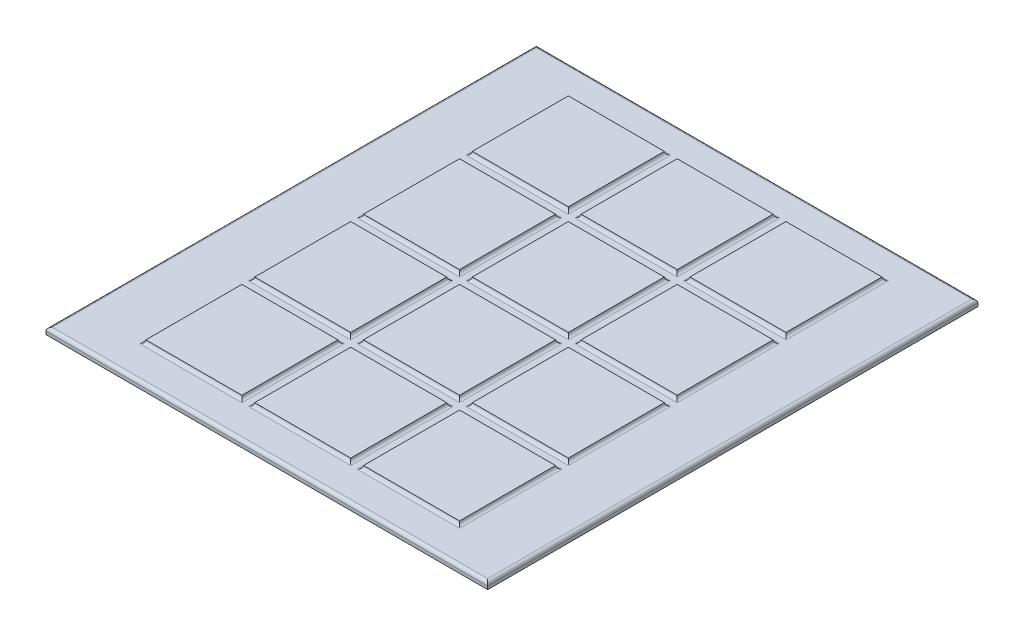
SolidWorks part; units mm, degrees
ref_plane "Front Plane" through (0, 0, 0) normal (0, 0, 1) x (1, 0, 0)
ref_plane "Top Plane" through (0, 0, 0) normal (0, 1, 0) x (1, 0, 0)
ref_plane "Right Plane" through (0, 0, 0) normal (1, 0, 0) x (0, 0, -1)
sketch "Sketch1" plane through (0, 0, 0) normal (0, 1, 0) x (1, 0, 0)
  line L1 (-34.5, 38.3) -> (34.5, 38.3)
  line L2 (-34.5, 38.3) -> (-34.5, -38.3)
  line L3 (-34.5, -38.3) -> (34.5, -38.3)
  line L4 (34.5, 38.3) -> (34.5, -38.3)
  point P4 (-34.5, 0)
  point P6 (0, 38.3)
  dimension "D1" = 76.6
  dimension "D2" = 69
extrude "Boss-Extrude1" add sketch "Sketch1" along normal blind 1 contours L2 L3 L4 L1
sketch "Sketch2" plane through (0, 1, 0) normal (0, 1, 0) x (1, 0, 0)
  line L0 (-24.5, 16.3) -> (-9.5, 16.3)
  line L1 (-24.5, 33.3) -> (-9.5, 33.3)
  line L2 (-24.5, 33.3) -> (-24.5, 18.3)
  line L3 (-24.5, 18.3) -> (-9.5, 18.3)
  line L4 (-9.5, 33.3) -> (-9.5, 18.3)
  line L5 (-7.5, 33.3) -> (7.5, 33.3)
  line L6 (-7.5, 33.3) -> (-7.5, 18.3)
  line L7 (-7.5, 18.3) -> (7.5, 18.3)
  line L8 (7.5, 33.3) -> (7.5, 18.3)
  line L9 (9.5, 33.3) -> (24.5, 33.3)
  line L10 (9.5, 33.3) -> (9.5, 18.3)
  line L11 (9.5, 18.3) -> (24.5, 18.3)
  line L12 (24.5, 33.3) -> (24.5, 18.3)
  line L13 (-24.5, 16.3) -> (-24.5, 1.3)
  line L14 (-24.5, 1.3) -> (-9.5, 1.3)
  line L15 (-9.5, 16.3) -> (-9.5, 1.3)
  line L16 (-7.5, 16.3) -> (7.5, 16.3)
  line L17 (-7.5, 16.3) -> (-7.5, 1.3)
  line L18 (-7.5, 1.3) -> (7.5, 1.3)
  line L19 (7.5, 16.3) -> (7.5, 1.3)
  line L20 (9.5, 16.3) -> (24.5, 16.3)
  line L21 (9.5, 16.3) -> (9.5, 1.3)
  line L22 (9.5, 1.3) -> (24.5, 1.3)
  line L23 (24.5, 16.3) -> (24.5, 1.3)
  line L24 (-24.5, -0.7) -> (-9.5, -0.7)
  line L25 (-24.5, -0.7) -> (-24.5, -15.7)
  line L26 (-24.5, -15.7) -> (-9.5, -15.7)
  line L27 (-9.5, -0.7) -> (-9.5, -15.7)
  line L28 (-7.5, -0.7) -> (7.5, -0.7)
  line L29 (-7.5, -0.7) -> (-7.5, -15.7)
  line L30 (-7.5, -15.7) -> (7.5, -15.7)
  line L31 (7.5, -0.7) -> (7.5, -15.7)
  line L32 (9.5, -0.7) -> (24.5, -0.7)
  line L33 (9.5, -0.7) -> (9.5, -15.7)
  line L34 (9.5, -15.7) -> (24.5, -15.7)
  line L35 (24.5, -0.7) -> (24.5, -15.7)
  line L36 (-24.5, -17.7) -> (-9.5, -17.7)
  line L37 (-24.5, -17.7) -> (-24.5, -32.7)
  line L38 (-24.5, -32.7) -> (-9.5, -32.7)
  line L39 (-9.5, -17.7) -> (-9.5, -32.7)
  line L40 (-7.5, -17.7) -> (7.5, -17.7)
  line L41 (-7.5, -17.7) -> (-7.5, -32.7)
  line L42 (-7.5, -32.7) -> (7.5, -32.7)
  line L43 (7.5, -17.7) -> (7.5, -32.7)
  line L44 (9.5, -17.7) -> (24.5, -17.7)
  line L45 (9.5, -17.7) -> (9.5, -32.7)
  line L46 (9.5, -32.7) -> (24.5, -32.7)
  line L47 (24.5, -17.7) -> (24.5, -32.7)
  line L48 (-34.5, 38.3) -> (34.5, 38.3) construction
  point P13 (0, 33.3)
  dimension "D1" = 2
  dimension "D2" = 2
  dimension "D3" = 15
  dimension "D4" = 4
  dimension "D5" = 5
extrude "Boss-Extrude2" add sketch "Sketch2" along normal blind 0.5
fillet "Fillet1" radius 0.5 52 edges at (17, 1, 32.7) (24.5, 1, 25.2) (17, 1, 17.7) (9.5, 1, 25.2) (-17, 1, 32.7) (-9.5, 1, 25.2) (-17, 1, 17.7) (-24.5, 1, 25.2) (0, 1, 15.7) (7.5, 1, 8.2) (0, 1, 0.7) (-7.5, 1, 8.2) (17, 1, -1.3) (24.5, 1, -8.8) (17, 1, -16.3) (9.5, 1, -8.8) (-17, 1, -1.3) (-9.5, 1, -8.8) (-17, 1, -16.3) (-24.5, 1, -8.8) (0, 1, -18.3) (7.5, 1, -25.8) (0, 1, -33.3) (-7.5, 1, -25.8) (34.5, 1, 0) (0, 1, 38.3) (-34.5, 1, 0) (0, 1, -38.3) (-17, 1, -18.3) (-9.5, 1, -25.8) (-17, 1, -33.3) (-24.5, 1, -25.8) (17, 1, -18.3) (24.5, 1, -25.8) (17, 1, -33.3) (9.5, 1, -25.8) (0, 1, -1.3) (7.5, 1, -8.8) (0, 1, -16.3) (-7.5, 1, -8.8) (-17, 1, 15.7) (-9.5, 1, 8.2) (-17, 1, 0.7) (-24.5, 1, 8.2) (17, 1, 15.7) (24.5, 1, 8.2) (17, 1, 0.7) (9.5, 1, 8.2) (0, 1, 32.7) (7.5, 1, 25.2) (0, 1, 17.7) (-7.5, 1, 25.2)
